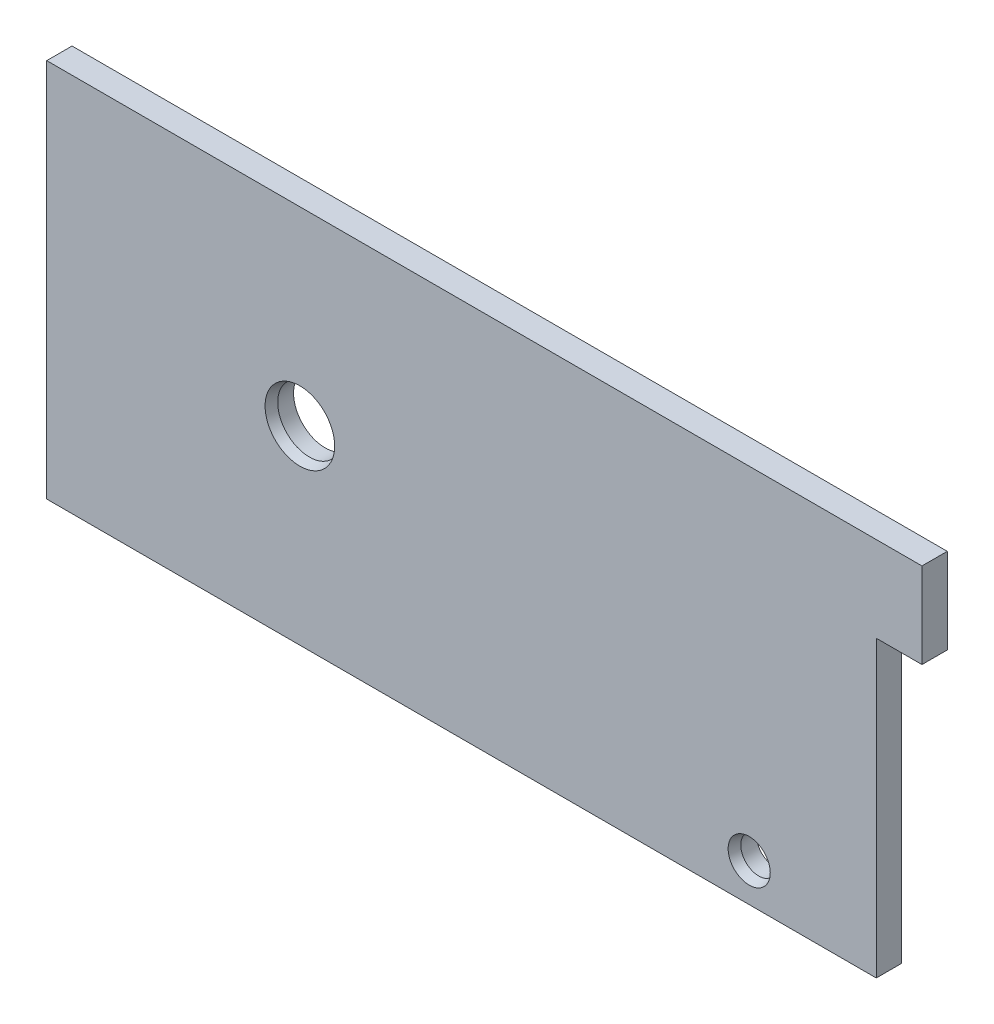
SolidWorks part; units mm, degrees
ref_plane "Front Plane" through (0, 0, 0) normal (0, 0, 1) x (1, 0, 0)
ref_plane "Top Plane" through (0, 0, 0) normal (0, 1, 0) x (1, 0, 0)
ref_plane "Right Plane" through (0, 0, 0) normal (1, 0, 0) x (0, 0, -1)
sketch "Sketch1" plane through (0, 0, 0) normal (0, 0, 1) x (1, 0, 0)
  line L1 (-81, -30) -> (50.0797, -30)
  line L6 (57.3, 16.5) -> (50.0797, 16.5)
  line L11 (57.3, 16.5) -> (57.3, 30)
  line L13 (50.0797, 16.5) -> (50.0797, -30)
  line L18 (57.3, 30) -> (-81, 30)
  line L19 (-81, 30) -> (-81, -30)
  circle A4 centre (-41, 0) radius 5
  circle A5 centre (30, -24) radius 2.83
  point P4 (-81, 0)
  dimension "D5" = 10
  dimension "D9" = 5.66
  dimension "D8" = 13.5
  dimension "D10" = 60
  dimension "D2" = 138.3
  dimension "D3" = 40
  dimension "D4" = 71
  dimension "D6" = 24
extrude "Boss-Extrude1" add sketch "Sketch1" along normal mid plane 4
chamfer "Chamfer1" distance 0.5 distance2 1.5 2 edges at (32.83, -24, 2) (-36, 0, 2) first distance on face at (-36, 0, 2)
equation "\"back_boost\"= 7"
equation "\"D3@Sketch1\"=\"back_boost\"+33.00mm"
equation "\"D2@Sketch1\"=\"back_boost\"+131.30mm"
